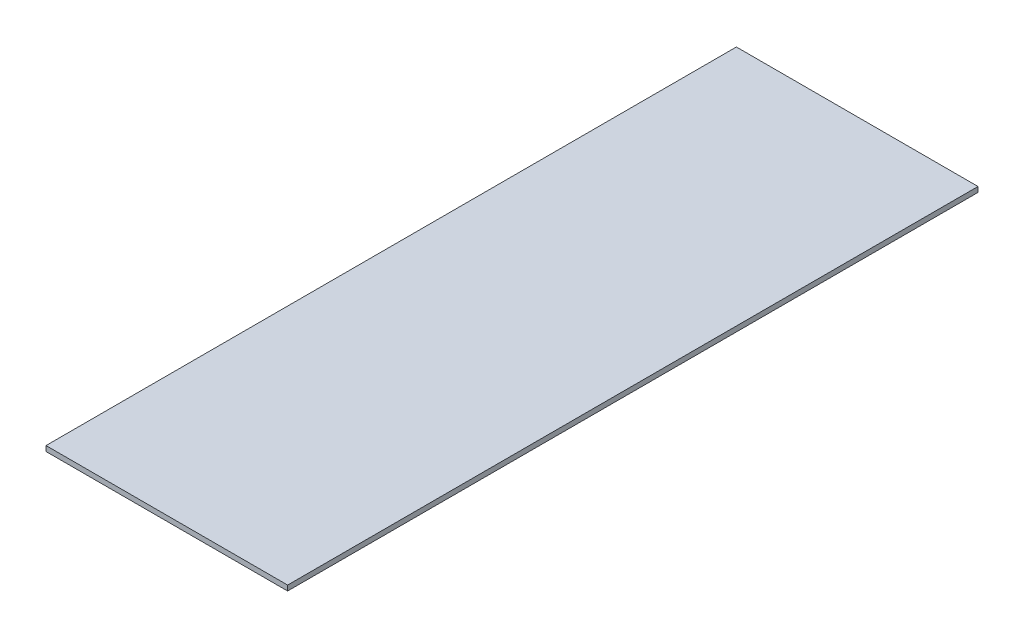
SolidWorks part; units mm, degrees
ref_plane "Front Plane" through (0, 0, 0) normal (0, 0, 1) x (1, 0, 0)
ref_plane "Top Plane" through (0, 0, 0) normal (0, 1, 0) x (1, 0, 0)
ref_plane "Right Plane" through (0, 0, 0) normal (1, 0, 0) x (0, 0, -1)
sketch "Sketch2" plane through (0, 0, 0) normal (0, 1, 0) x (1, 0, 0)
  line L1 (0, 0) -> (140, 0)
  line L2 (0, 0) -> (0, 400)
  line L3 (0, 400) -> (140, 400)
  line L4 (140, 0) -> (140, 400)
  dimension "D1" = 400
  dimension "D2" = 140
extrude "Boss-Extrude1" add sketch "Sketch2" along normal blind 3
